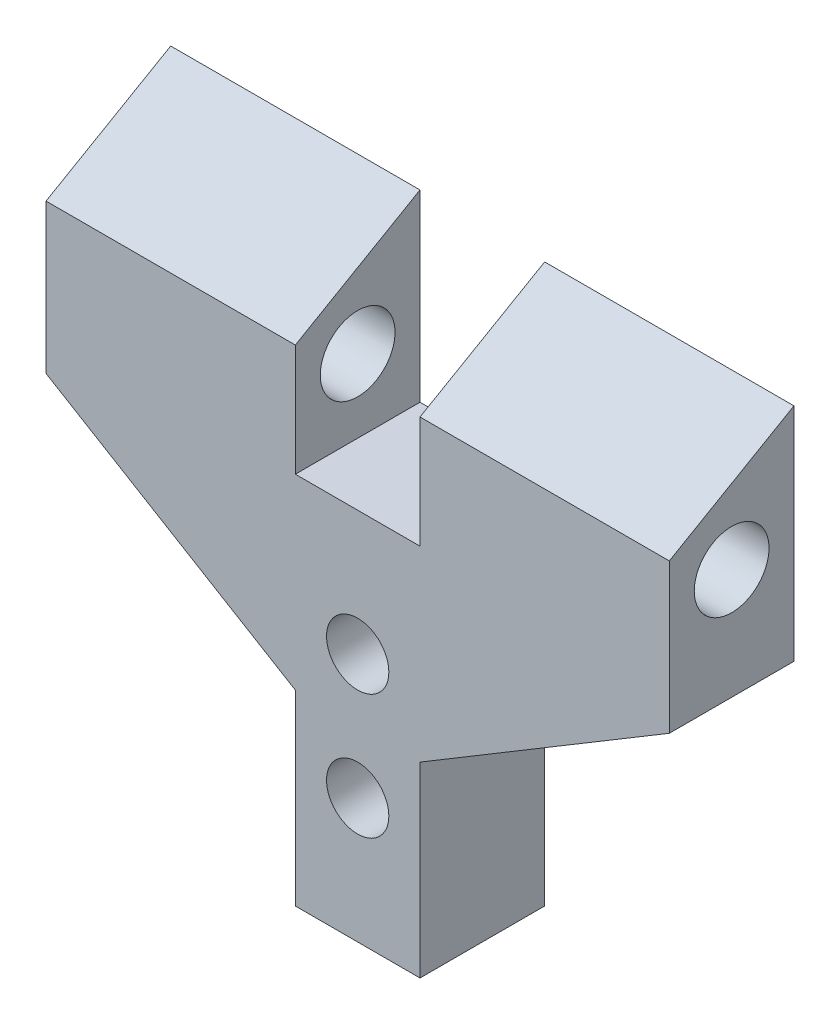
SolidWorks part; units mm, degrees
ref_plane "Plan de face" through (0, 0, 0) normal (0, 0, 1) x (1, 0, 0)
ref_plane "Plan de dessus" through (0, 0, 0) normal (0, 1, 0) x (1, 0, 0)
ref_plane "Plan de droite" through (0, 0, 0) normal (1, 0, 0) x (0, 0, -1)
sketch "Esquisse1" plane through (0, 0, 0) normal (0, 0, 1) x (1, 0, 0)
  line L0 (-25, 12) -> (-5, 0)
  line L1 (-5, -15) -> (5, -15)
  line L2 (-5, -15) -> (-5, 0)
  line L3 (-5, 15) -> (5, 15)
  line L4 (5, -15) -> (5, 0)
  line L5 (-5, -15) -> (5, 15) construction
  line L6 (-5, 15) -> (5, -15) construction
  line L8 (-5, 15) -> (-5, 29.75)
  line L9 (-5, 29.75) -> (-25, 29.75)
  line L10 (-25, 12) -> (-25, 29.75)
  line L12 (5, 15) -> (5, 29.75)
  line L13 (5, 29.75) -> (25, 29.75)
  line L14 (25, 12) -> (25, 29.75)
  line L15 (5, 0) -> (25, 12)
  circle A0 centre (0, -5) radius 2.5
  circle A1 centre (0, 5) radius 2.5
  point P0 (0, 3.5555)
  dimension "D3" = 10
  dimension "D4" = 5
  dimension "D11" = 5
  dimension "D1" = 30
  dimension "D2" = 10
  dimension "D5" = 5
  dimension "D8" = 17.75
  dimension "D9" = 17.75
extrude "Boss.-Extru.1" add sketch "Esquisse1" along normal blind 10 contours L10 L2 L8 L9 | L1 L4 L3 L2 A1 | L14 L13 L12 L4 region at (0, 13.8274, 0)
sketch "Esquisse2" plane through (-25, 0, 0) normal (-1, 0, 0) x (0, 0, 1)
  line L0 (0, 29.75) -> (10, 29.75)
  line L1 (10, 29.75) -> (10, 23.9765)
  line L2 (10, 12) -> (10, 29.75) construction
  line L3 (10, 23.9765) -> (0, 29.75)
  line L4 (0, 29.75) -> (10, 12) construction
  line L5 (10, 12) -> (10, 20.875) construction
  line L6 (10, 20.875) -> (5, 20.875) construction
  circle A0 centre (5, 20.875) radius 3
  dimension "D2" = 6
  dimension "D1" = 30
extrude "Enlèv. mat.-Extru.1" cut sketch "Esquisse2" against normal up to surface (50 mm away) up to face at (25, 20.875, 5)
